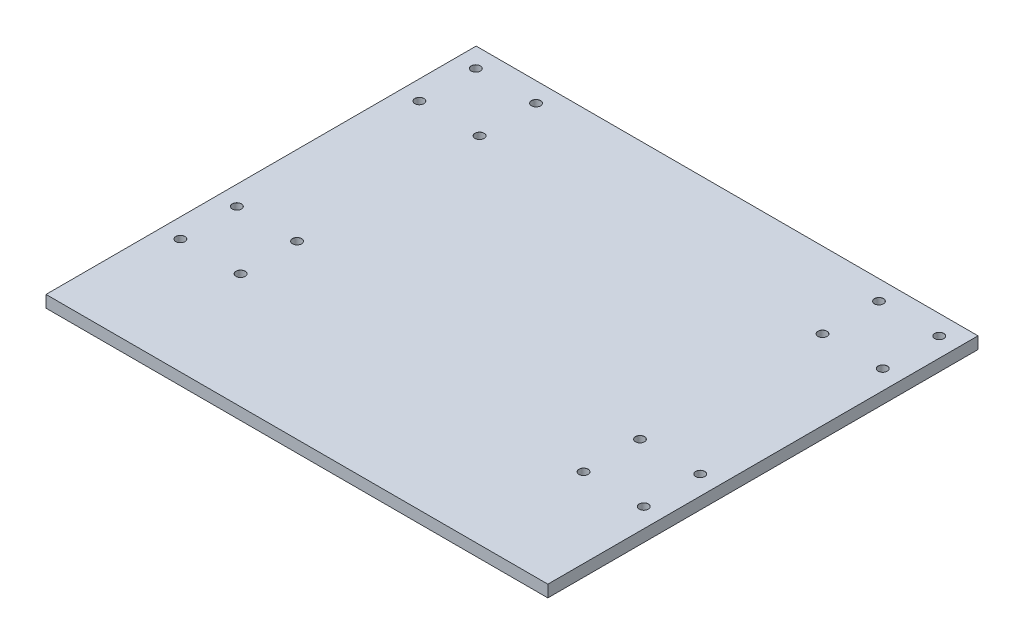
SolidWorks part; units mm, degrees
ref_plane "Front Plane" through (0, 0, 0) normal (0, 0, 1) x (1, 0, 0)
ref_plane "Top Plane" through (0, 0, 0) normal (0, 1, 0) x (1, 0, 0)
ref_plane "Right Plane" through (0, 0, 0) normal (1, 0, 0) x (0, 0, -1)
sketch "Sketch1" plane through (0, 0, 0) normal (0, 1, 0) x (1, 0, 0)
  line L1 (-133.35, 114.3) -> (133.35, 114.3)
  line L2 (-133.35, 114.3) -> (-133.35, -114.3)
  line L3 (-133.35, -114.3) -> (133.35, -114.3)
  line L4 (133.35, 114.3) -> (133.35, -114.3)
  line L5 (-133.35, 114.3) -> (133.35, -114.3) construction
  line L6 (-133.35, -114.3) -> (133.35, 114.3) construction
  point P0 (0, 0)
  dimension "D1" = 266.7
  dimension "D2" = 228.6
extrude "Boss-Extrude1" add sketch "Sketch1" along normal blind 6.35
ref_plane "Top" through (0, 0, -114.3) normal (0, 0, -1) x (-1, 0, 0)
hole_wizard "M4 Clearance Hole1" positions "Sketch2" profile "Sketch3" hole size "M4" standard "ANSI Metric" end condition up to next
sketch "Sketch2" plane through (0, 6.35, 0) normal (0, 1, 0) x (1, 0, 0)
  circle A0 centre (123.125, 103.9) radius 2.5 construction
  circle A1 centre (91.125, 103.9) radius 2.5 construction
  circle A2 centre (91.125, 73.9) radius 2.5 construction
  circle A3 centre (123.125, -53.1) radius 2.5 construction
  circle A4 centre (123.125, -23.1) radius 2.5 construction
  circle A5 centre (123.125, 73.9) radius 2.5 construction
  circle A6 centre (-123.125, 103.9) radius 2.5 construction
  circle A7 centre (-91.125, 103.9) radius 2.5 construction
  circle A8 centre (-91.125, 73.9) radius 2.5 construction
  circle A9 centre (91.125, -23.1) radius 2.5 construction
  circle A10 centre (91.125, -53.1) radius 2.5 construction
  circle A11 centre (-123.125, -53.1) radius 2.5 construction
  circle A12 centre (-91.125, -53.1) radius 2.5 construction
  circle A13 centre (-91.125, -23.1) radius 2.5 construction
  circle A14 centre (-123.125, -23.1) radius 2.5 construction
  circle A15 centre (-123.125, 73.9) radius 2.5 construction
  circle A16 centre (123.125, 103.9) radius 2.5 construction
  circle A17 centre (91.125, 103.9) radius 2.5 construction
  circle A18 centre (91.125, 73.9) radius 2.5 construction
  circle A19 centre (123.125, -53.1) radius 2.5 construction
  circle A20 centre (123.125, -23.1) radius 2.5 construction
  circle A21 centre (123.125, 73.9) radius 2.5 construction
  circle A22 centre (-123.125, 103.9) radius 2.5 construction
  circle A23 centre (-91.125, 103.9) radius 2.5 construction
  circle A24 centre (-91.125, 73.9) radius 2.5 construction
  circle A25 centre (91.125, -23.1) radius 2.5 construction
  circle A26 centre (91.125, -53.1) radius 2.5 construction
  circle A27 centre (-123.125, -53.1) radius 2.5 construction
  circle A28 centre (-91.125, -53.1) radius 2.5 construction
  circle A29 centre (-91.125, -23.1) radius 2.5 construction
  circle A30 centre (-123.125, -23.1) radius 2.5 construction
  circle A31 centre (-123.125, 73.9) radius 2.5 construction
  point P1 (123.125, 103.9)
  point P3 (91.125, 103.9)
  point P5 (91.125, 73.9)
  point P7 (123.125, -53.1)
  point P9 (123.125, -23.1)
  point P11 (123.125, 73.9)
  point P13 (-123.125, 103.9)
  point P15 (-91.125, 103.9)
  point P17 (-91.125, 73.9)
  point P21 (91.125, -53.1)
  point P23 (-123.125, -53.1)
  point P25 (-91.125, -53.1)
  point P27 (-91.125, -23.1)
  point P29 (-123.125, -23.1)
  point P31 (-123.125, 73.9)
  point P71 (91.125, -23.1)
sketch "Sketch3" plane through (123.125, 6.35, -103.9) normal (1, 0, 0) x (0, 0, 1)
  line L0 (0, 0) -> (0, 6.35)
  line L1 (0, 6.35) -> (2.4, 6.35)
  line L2 (2.4, 6.35) -> (2.4, 0.025)
  line L3 (2.4, 0.025) -> (2.425, 0)
  line L5 (2.425, 0) -> (0, 0)
  line L6 (-2.4, 0.025) -> (-2.425, 0) construction
  line L11 (0, -6.35) -> (0, 107.95) construction
  dimension "Thru Hole Dia." = 4.8
  dimension "Thru Hole Depth" = 6.35
  dimension "Near C'Sink Dia." = 4.85
  dimension "Near C'Sink Angle" = 90
